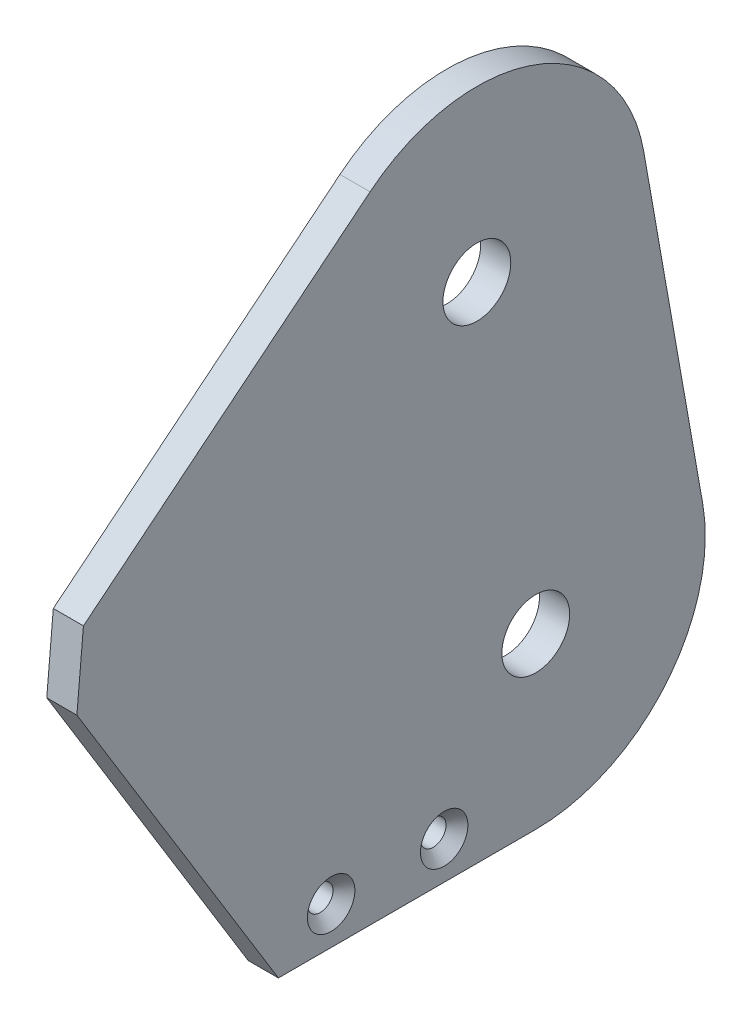
SolidWorks part; units mm, degrees
ref_plane "Front Plane" through (0, 0, 0) normal (0, 0, 1) x (1, 0, 0)
ref_plane "Top Plane" through (0, 0, 0) normal (0, 1, 0) x (1, 0, 0)
ref_plane "Right Plane" through (0, 0, 0) normal (1, 0, 0) x (0, 0, -1)
ref_plane "Plane1" through (25, 0, 0) normal (1, 0, 0) x (0, 0, -1)
sketch "Sketch2" plane through (25, 0, 0) normal (1, 0, 0) x (0, 0, -1)
  line L0 (26.5013, 109.2234) -> (34.3155, 64.9071)
  line L1 (12.1573, 38.5) -> (-22, 38.5)
  line L2 (-22, 38.5) -> (-48.7484, 82.0825)
  line L3 (-48.7484, 82.0825) -> (-47.8793, 91.9182)
  line L4 (-47.8793, 91.9182) -> (-9.8336, 122.7883)
  circle A0 centre (12.1573, 61) radius 22.5 construction
  circle A1 centre (4.3431, 105.3163) radius 22.5 construction
  arc A2 (12.1573, 38.5) -> (34.3155, 64.9071) centre (12.1573, 61) ccw
  arc A3 (26.5013, 109.2234) -> (-9.8336, 122.7883) centre (4.3431, 105.3163) ccw
  circle A4 centre (-15, 43.5) radius 3.1263 construction
  circle A5 centre (0, 43.5) radius 3.1263 construction
  dimension "D4" = 2
  dimension "D5" = 15
  dimension "D6" = 5
extrude "Boss-Extrude1" add sketch "Sketch2" along normal blind 4
hole_wizard "Hole1" positions "Sketch3" profile "Sketch4" legacy
sketch "Sketch3" plane through (25, 0, 0) normal (-1, 0, 0) x (0, 0, 1)
  point P0 (-4.3431, 105.3163)
  point P3 (-12.1573, 61)
sketch "Sketch4" plane through (25, 105.3163, -4.3431) normal (0, 1, 0) x (0, 0, 1)
  line L0 (0, 0) -> (0, 100)
  line L1 (0, 100) -> (4.5, 100)
  line L2 (4.5, 100) -> (4.5, 0)
  line L3 (4.5, 0) -> (0, 0)
  line L4 (0, 110) -> (0, -10) construction
  dimension "Diameter" = 9
  dimension "Depth" = 100
hole_wizard "CSK for M3 Flat Head Machine Screw1" positions "Sketch9" profile "Sketch8" countersink size "M3" standard "ANSI Metric" end condition through all
sketch "Sketch9" plane through (29, 0, 0) normal (1, 0, 0) x (0, 0, -1)
  point P0 (0, 43.5)
  point P3 (-15, 43.5)
sketch "Sketch8" plane through (29, 43.5, 0) normal (0, 1, 0) x (0, 0, -1)
  line L0 (0, 0) -> (0, 4)
  line L1 (0, 4) -> (1.7, 4)
  line L2 (1.7, 4) -> (1.7, 1.45)
  line L3 (1.7, 1.45) -> (3.15, 0)
  line L5 (3.15, 0) -> (0, 0)
  line L6 (-1.7, 1.45) -> (-3.15, 0) construction
  line L11 (0, -6.35) -> (0, 107.95) construction
  dimension "Thru Hole Dia." = 3.4
  dimension "Thru Hole Depth" = 4
  dimension "Near C'Sink Dia." = 6.3
  dimension "Near C'Sink Angle" = 90
